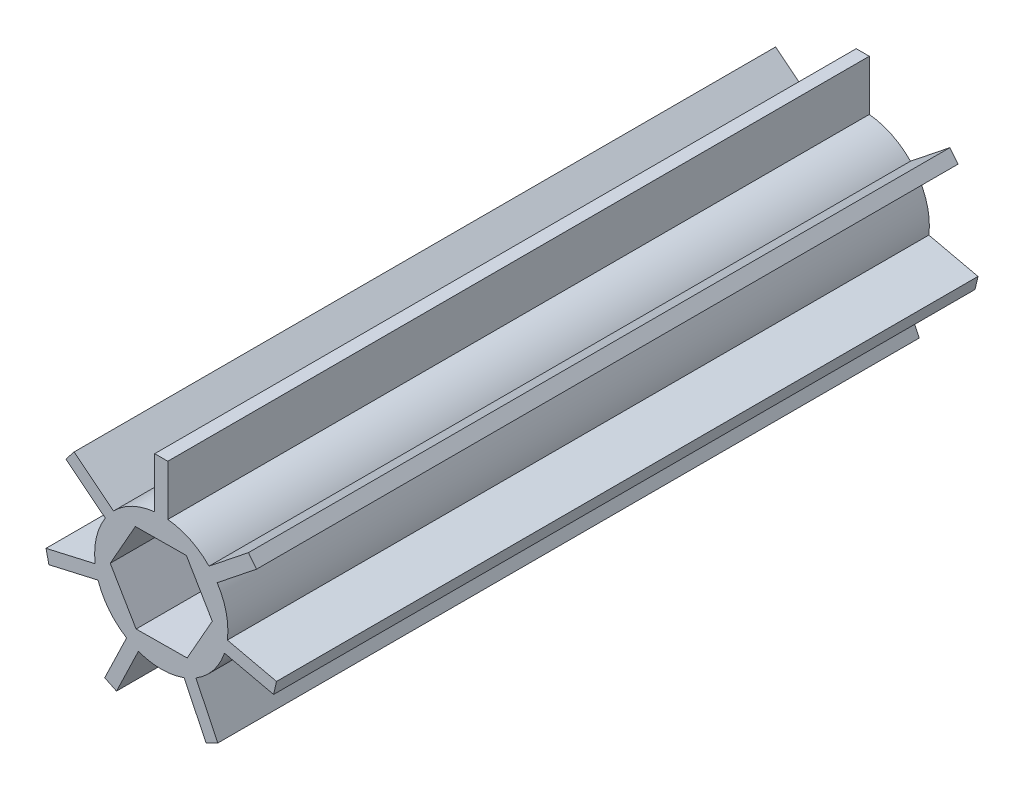
SolidWorks part; units mm, degrees
ref_plane "Front Plane" through (0, 0, 0) normal (0, 0, 1) x (1, 0, 0)
ref_plane "Top Plane" through (0, 0, 0) normal (0, 1, 0) x (1, 0, 0)
ref_plane "Right Plane" through (0, 0, 0) normal (1, 0, 0) x (0, 0, -1)
sketch "Sketch1" plane through (0, 0, 0) normal (0, 0, 1) x (1, 0, 0)
  circle A0 centre (0, 0) radius 12.7
  dimension "D1" = 25.4
sketch "Sketch6" plane through (0, 0, 0) normal (0, 0, 1) x (1, 0, 0)
  circle A0 centre (0, 0) radius 7.239
  dimension "D1" = 14.478
sketch "Sketch8" plane through (0, 0, 0) normal (0, 0, 1) x (1, 0, 0)
  line L1 (5.5431, 0.0471) -> (2.7307, 4.824)
  line L2 (2.7307, 4.824) -> (-2.8123, 4.7769)
  line L3 (-2.8123, 4.7769) -> (-5.5431, -0.0471)
  line L4 (-5.5431, -0.0471) -> (-2.7307, -4.824)
  line L5 (-2.7307, -4.824) -> (2.8123, -4.7769)
  line L6 (2.8123, -4.7769) -> (5.5431, 0.0471)
  circle A0 centre (0, 0) radius 4.8006 construction
  dimension "D1" = 4.8006
sketch "Sketch12" plane through (0, 0, 0) normal (0, 0, 1) x (1, 0, 0)
  line L0 (0, 0) -> (0.7112, 0)
  line L2 (-0.7112, 0) -> (-0.7112, 12.6801)
  line L3 (-0.7112, 12.6801) -> (0.7112, 12.6801)
  line L4 (0.7112, 0) -> (0.7112, 12.6801)
  line L5 (0, 0) -> (0.7112, 12.6801) construction
  line L6 (-0.7112, 12.6801) -> (0, 0) construction
  line L7 (0, 0) -> (-0.7112, 0)
  circle A0 centre (0, 0) radius 12.7 construction
  point P0 (0, 0)
  dimension "D1" = 1.4224
extrude "Boss-Extrude1" add sketch "Sketch12" against normal blind 76.2
extrude "Boss-Extrude2" add sketch "Sketch6" against normal blind 76.2 contours A0
ref_axis "Axis1" through (0, 0, -76.2) along (0, 0, 1)
pattern_circular "CirPattern1" count 7 over 360 about axis through (0, 0, -76.2) along (0, 0, 1) of "Boss-Extrude1"
extrude "Cut-Extrude5" cut sketch "Sketch8" against normal through all
